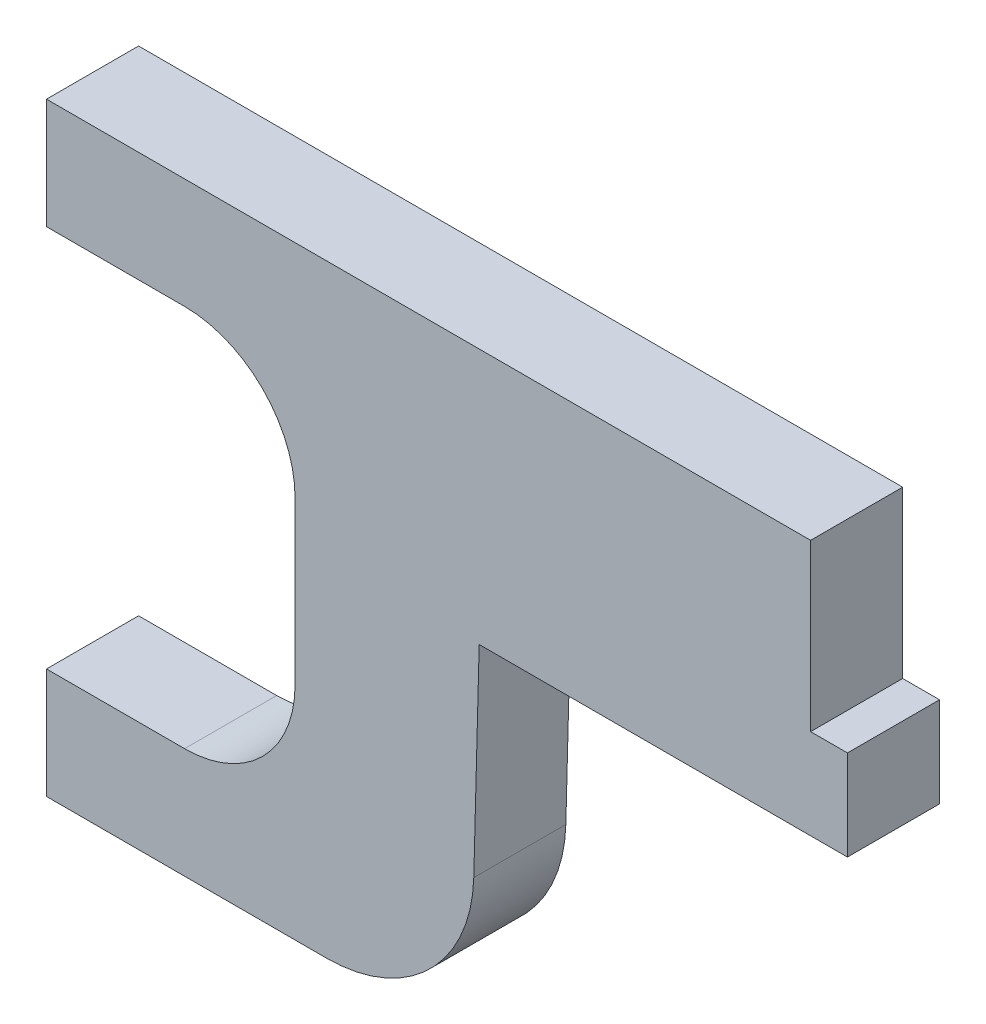
SolidWorks part; units mm, degrees
material "PBT General Purpose"
ref_plane "Front Plane" through (0, 0, 0) normal (0, 0, 1) x (1, 0, 0)
ref_plane "Top Plane" through (0, 0, 0) normal (0, 1, 0) x (1, 0, 0)
ref_plane "Right Plane" through (0, 0, 0) normal (1, 0, 0) x (0, 0, -1)
sketch "frame_outline" plane through (0, 0, 0) normal (0, 0, 1) x (1, 0, 0)
  line L89 (0, 1.64) -> (0, 1.34)
  line L99 (0, 1.34) -> (0.675, 1.34)
  line L100 (0.675, 1.34) -> (0.675, 0.3)
  line L101 (0.675, 0.3) -> (0, 0.3)
  line L102 (0, 0.3) -> (0, 0)
  line L103 (0, 0) -> (1.15, 0)
  line L105 (1.15, 0) -> (1.175, 0.945)
  line L108 (2.075, 1.64) -> (0.7, 1.64)
  line L109 (0.7, 1.64) -> (0, 1.64)
  line L110 (0.675, 0.82) -> (2.391, 0.82) construction
  line L112 (1.175, 0.945) -> (2.175, 0.945)
  line L113 (2.175, 0.945) -> (2.175, 1.19)
  line L115 (2.075, 1.64) -> (2.075, 1.19)
  line L116 (2.075, 1.19) -> (2.175, 1.19)
  dimension "D2" = 0.3
  dimension "D9" = 1.64
  dimension "D10" = 0.675
  dimension "D14" = 1.15
  dimension "D15" = 0.7
  dimension "D4" = 1
  dimension "D5" = 0.5
  dimension "D7" = 0.45
  dimension "D3" = 0.125
  dimension "D6" = 0.1
  dimension "D8" = 0.245
  dimension "D11" = 0.695
extrude "Boss-Extrude1" add sketch "frame_outline" along normal mid plane 0.25
fillet "Fillet1" radius 0.3 2 edges at (0.675, 0.3, 0) (0.675, 1.34, 0)
fillet "Fillet2" radius 0.4 1 edges at (1.15, 0, 0)
equation "\"t\"= 0.25'thickness of the sheets"
equation "\"t_cf\"= 0.115'thickness of single carbon fiber layer"
equation "\"t_kapton\"= 0.025'thickness of single Kapton flex layer"
equation "\"t_fr4\"= 0.1'thickness of FR4 with copper layer"
equation "\"joint_flex\"= 0.1'Width of flextures gap"
equation "\"joint_flex_eff\"= 0.02'Width of flecture after castelation"
equation "\"joint_fold\"= 0.2'Width of folding joints for 90deg fold"
equation "\"gap_tolerance\"= 0.002'Width to have interfecence fit between carbon fiber inserts"
equation "\"assemble_angle\"= 90'Angle of assembly parts"
equation "\"D1@Boss-Extrude1\"=\"t\""
equation "\"link_lift\"= 0.5'Actuation linkage amplification for the lift motion"
equation "\"link_swing\"= 0.45'Actuation linkage amplification for the swing motion"
equation "\"D10@frame_outline\"=\"t\"*1.5+0.3+0.1-\"joint_flex\""
equation "\"D3@frame_outline\"=\"t\"/2"
equation "\"D6@frame_outline\"=\"joint_fold\"/2"
equation "\"D7@frame_outline\"=0.40mm+0.05"
